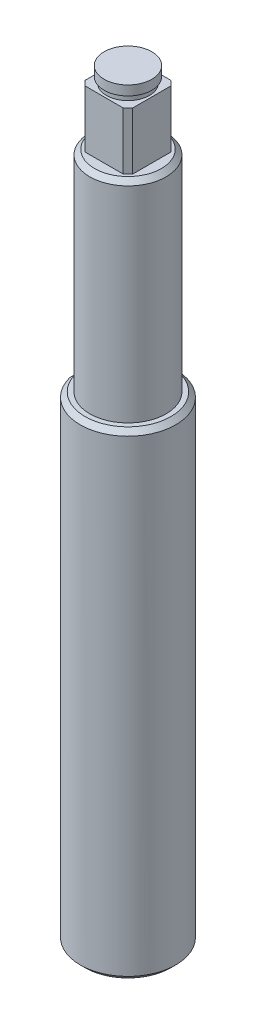
SolidWorks part; units mm, degrees
ref_plane "前视基准面" through (0, 0, 0) normal (0, 0, 1) x (1, 0, 0)
ref_plane "上视基准面" through (0, 0, 0) normal (0, 1, 0) x (1, 0, 0)
ref_plane "右视基准面" through (0, 0, 0) normal (1, 0, 0) x (0, 0, -1)
sketch "草图1" plane through (0, 0, 0) normal (0, 1, 0) x (1, 0, 0)
  circle A0 centre (0, 0) radius 5
  dimension "D1" = 10
extrude "凸台-拉伸1" add sketch "草图1" along normal mid plane 50
sketch "草图2" plane through (0, 25, 0) normal (0, 1, 0) x (1, 0, 0)
  circle A0 centre (0, 0) radius 4
  dimension "D1" = 8
extrude "凸台-拉伸2" add sketch "草图2" along normal blind 22
sketch "草图3" plane through (0, 47, 0) normal (0, 1, 0) x (1, 0, 0)
  line L1 (-2.5, -2.5) -> (2.5, -2.5)
  line L2 (-2.5, -2.5) -> (-2.5, 2.5)
  line L3 (-2.5, 2.5) -> (2.5, 2.5)
  line L4 (2.5, -2.5) -> (2.5, 2.5)
  line L5 (-2.5, -2.5) -> (2.5, 2.5) construction
  line L6 (-2.5, 2.5) -> (2.5, -2.5) construction
  point P0 (0, 0)
  dimension "D1" = 5
extrude "凸台-拉伸3" add sketch "草图3" along normal blind 6
sketch "草图4" plane through (0, 53, 0) normal (0, 1, 0) x (1, 0, 0)
  circle A0 centre (0, 0) radius 2.5
  dimension "D1" = 5
extrude "凸台-拉伸4" add sketch "草图4" along normal offset from surface (1.6 mm away) 79.6 up to face at (0, -25, 5)
sketch "草图5" plane through (0, 53, 0) normal (0, 1, 0) x (1, 0, 0)
  circle A0 centre (0, 0) radius 2.25
  dimension "D1" = 4.5
extrude "切除-拉伸1" cut sketch "草图5" along normal blind 0.6 flip side to cut
ref_plane "基准面1" through (-5, 0, 0) normal (-1, 0, 0) x (0, 0, 1)
sketch "草图6" plane through (-5, 0, 0) normal (-1, 0, 0) x (0, 0, 1)
  line L0 (0, 38) -> (0, 12) construction
  line L1 (5, 25) -> (-5, 25) construction
  line L2 (1.25, 38) -> (1.25, 12)
  line L3 (-1.25, 38) -> (-1.25, 12)
  arc A0 (1.25, 38) -> (-1.25, 38) centre (0, 38) ccw
  arc A1 (-1.25, 12) -> (1.25, 12) centre (0, 12) ccw
  point P5 (0, 25)
  dimension "D1" = 13
  dimension "D2" = 2.5
extrude "切除-拉伸2" cut sketch "草图6" against normal blind 0.9
chamfer "倒角1" distance 0.5 angle 45 3 edges at (0, 47, 4) (0, -25, 5) (5, 25, 0)
chamfer "倒角2" distance 0.5 angle 45 4 edges at (2.5, 49.9822, 2.5) (2.5, 49.9822, -2.5) (-2.5, 49.9822, 2.5) (-2.5, 49.9822, -2.5)
